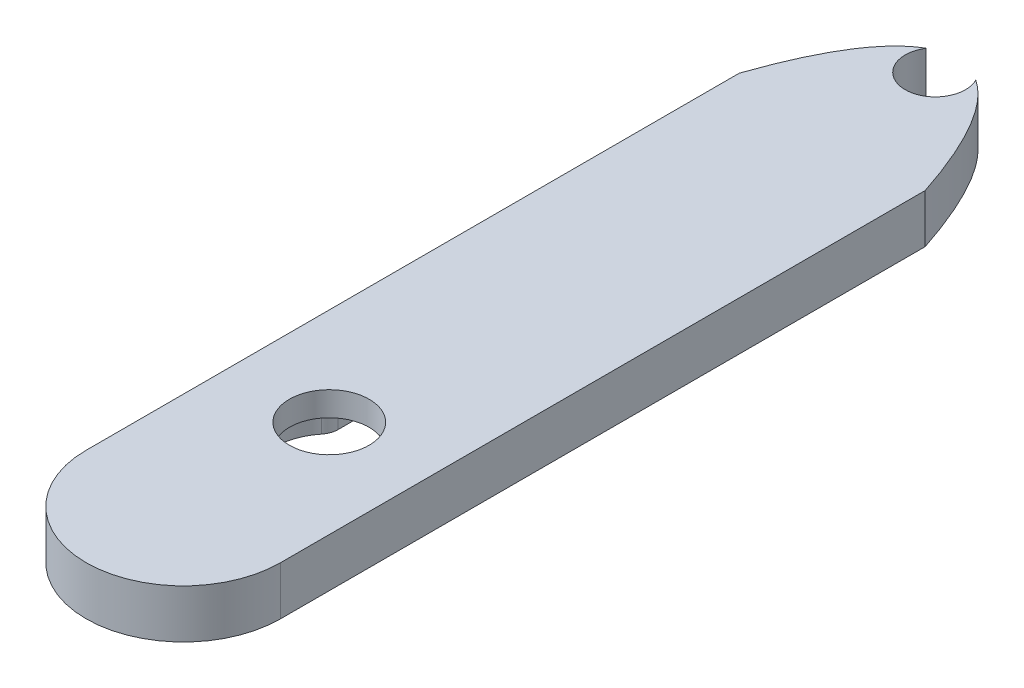
SolidWorks part; units mm, degrees
ref_plane "Front Plane" through (0, 0, 0) normal (0, 0, 1) x (1, 0, 0)
ref_plane "Top Plane" through (0, 0, 0) normal (0, 1, 0) x (1, 0, 0)
ref_plane "Right Plane" through (0, 0, 0) normal (1, 0, 0) x (0, 0, -1)
sketch "Sketch1" plane through (0, 0, 0) normal (0, 1, 0) x (1, 0, 0)
  line L0 (0, 0) -> (0, 12.7862) construction
  line L16 (-23.6152, 0) -> (23.6152, 0) construction
  line L22 (-3.8884, 4.0299) -> (-3.8884, 8.5053)
  line L23 (-3.8177, 9.3432) -> (-2.6646, 16.1267)
  line L24 (3.8299, 9.3786) -> (2.6768, 16.1621)
  line L25 (3.9006, 4.0181) -> (3.9006, 8.5407)
  line L26 (-3.8945, -4.024) -> (-3.8945, -8.5406)
  line L27 (-3.8238, -9.3786) -> (-2.6707, -16.1621)
  line L28 (3.8238, -9.3786) -> (2.6707, -16.1621)
  line L29 (3.8945, -4.024) -> (3.8945, -8.5406)
  line L30 (-10, 62.3) -> (-10, 25)
  line L31 (-7.5, 22.5) -> (7.5, 22.5)
  line L32 (-7.5, 22.5) -> (-7.5, -22.5)
  line L33 (-7.5, -22.5) -> (7.5, -22.5)
  line L34 (7.5, 22.5) -> (7.5, -22.5)
  line L35 (-7.5, 22.5) -> (7.5, -22.5) construction
  line L36 (-7.5, -22.5) -> (7.5, 22.5) construction
  line L41 (-10, 25) -> (10, 25)
  line L42 (-10, 25) -> (-10, -25)
  line L43 (-10, -25) -> (10, -25)
  line L44 (10, 25) -> (10, -25)
  line L45 (-10, 25) -> (10, 25)
  line L46 (-10, 25) -> (-10, 62.3)
  line L48 (10, 25) -> (10, 62.3)
  line L49 (10, 62.3) -> (10, 25)
  arc A8 (-2.5939, 16.9879) -> (2.606, 17) centre (0.006, 17) cw
  arc A9 (-2.6, -17) -> (2.6, -17) centre (0, -17) ccw
  circle A10 centre (0, 0) radius 5.6
  circle A11 centre (0, 0) radius 1.6
  circle A13 centre (0, 0) radius 4.1
  arc A14 (2.6, -17) -> (2.6707, -16.1621) centre (7.6, -17) cw
  arc A15 (-2.6707, -16.1621) -> (-2.6, -17) centre (-7.6, -17) cw
  arc A16 (-3.8945, -8.5406) -> (-3.8238, -9.3786) centre (1.1055, -8.5406) ccw
  arc A17 (3.8238, -9.3786) -> (3.8945, -8.5406) centre (-1.1055, -8.5406) ccw
  arc A18 (2.606, 17) -> (2.6768, 16.1621) centre (7.606, 17) ccw
  arc A19 (-2.6646, 16.1267) -> (-2.5939, 16.9879) centre (-7.5939, 16.9647) ccw
  arc A20 (3.8299, 9.3786) -> (3.9006, 8.5407) centre (-1.0994, 8.5407) cw
  arc A21 (-3.8884, 8.5053) -> (-3.8177, 9.3432) centre (1.1116, 8.5053) cw
  circle A22 centre (0, 62.3) radius 3.1
  arc A23 (-10, 62.3) -> (10, 62.3) centre (0, 62.3) cw
  point P14 (0, 0)
  point P49 (0, 19.6)
  point P50 (0, -19.6)
  dimension "D1" = 11.2
  dimension "D2" = 3.2
  dimension "D7" = 50
  dimension "D3" = 15
  dimension "D4" = 8.2
  dimension "D8" = 5
  dimension "D12" = 6.2
  dimension "D14" = 10
  dimension "D5" = 45
  dimension "D6" = 20
  dimension "D9" = 19.6
  dimension "D10" = 19.6
  dimension "D11" = 2.5
  dimension "D13" = 62.3
extrude "Boss-Extrude1" add sketch "Sketch1" against normal blind 2.2 contours L34 L31 L32 L33 A10 L29 L28 A9 L27 L26 L22 L23 A8 L24 L25 region at (0, 0, -22.0257)
extrude "Boss-Extrude2" add sketch "Sketch1<3>" against normal blind 2.5 contours L44 L41 L42 L43 L31 L34 L33 L32 | L34 L31 L32 L33 L22 A21 L23 A19 A8 A18 L24 A20 L25 A10 L29 A17 L28 A14 A9 A15 L27 A16 L26 region at (0, 0, -24.4615) region at (0, 0, -22.0257)
sketch "Sketch1<3>" plane through (0, 0, 0) normal (0, 1, 0) x (1, 0, 0) same geometry as "Sketch1"
extrude "Boss-Extrude3" add sketch "Sketch1<4>" along normal blind 2.5 contours L34 L31 L32 L33 A10 L29 L28 A9 L27 L26 L22 L23 A8 L24 L25 | A10 L25 L24 A8 L23 L22 | A10 L26 L27 A9 L28 L29 | L44 L41 L42 L43 L31 L34 L33 L32 | A10 A13 region at (0.0082, 0, -11.4698) region at (0.0082, 0, -5.4416) region at (0, 0, 11.4704) region at (0, 0, -24.4615) region at (0, 0, -22.0257)
sketch "Sketch1<4>" plane through (0, 0, 0) normal (0, 1, 0) x (1, 0, 0) same geometry as "Sketch1"
fillet "Fillet1" radius 2 4 edges at (3.8945, -1.25, 4.024) (-3.8945, -1.25, 4.024) (-3.8884, -1.25, -4.0299) (3.9006, -1.25, -4.0181)
extrude "Boss-Extrude4" add sketch "Sketch1<5>" along normal mid plane 5 contours A23 L30 L41 L48 A22 region at (0, 0, -47.1248)
sketch "Sketch1<5>" plane through (0, 0, 0) normal (0, 1, 0) x (1, 0, 0) same geometry as "Sketch1"
fillet "Fillet2" radius 10 2 edges at (10, 0, 25) (-10, 0, 25)
sketch "Sketch2" plane through (0, -2.5, 0) normal (0, -1, 0) x (1, 0, 0)
  line L30 (5.7735, -40.7449) -> (-2.8868, -35.7449)
  line L31 (5.9735, -40.7449) -> (-2.9868, -35.5717)
  line L32 (-2.8868, -45.7449) -> (5.7735, -40.7449)
  line L33 (-2.9868, -45.9181) -> (5.9735, -40.7449)
  line L34 (-2.8868, -35.7449) -> (-2.8868, -45.7449)
  line L35 (-2.9868, -35.5717) -> (-2.9868, -45.9181)
  line L36 (5.7735, -24.7449) -> (-2.8868, -19.7449)
  line L37 (5.9735, -24.7449) -> (-2.9868, -19.5717)
  line L38 (-2.8868, -29.7449) -> (5.7735, -24.7449)
  line L39 (-2.9868, -29.9181) -> (5.9735, -24.7449)
  line L40 (-2.8868, -19.7449) -> (-2.8868, -29.7449)
  line L41 (-2.9868, -19.5717) -> (-2.9868, -29.9181)
  line L48 (-3.0868, -48.7449) -> (5.8735, -43.5717)
  line L49 (5.8735, -43.5717) -> (5.8735, -53.9181)
  line L50 (5.8735, -53.9181) -> (-3.0868, -48.7449)
  line L51 (5.7735, -53.7449) -> (-2.8868, -48.7449)
  line L52 (-2.8868, -48.7449) -> (5.7735, -43.7449)
  line L53 (5.7735, -43.7449) -> (5.7735, -53.7449)
  line L54 (-3.0868, -32.7449) -> (5.8735, -27.5717)
  line L55 (5.8735, -27.5717) -> (5.8735, -37.9181)
  line L56 (5.8735, -37.9181) -> (-3.0868, -32.7449)
  line L57 (5.7735, -37.7449) -> (-2.8868, -32.7449)
  line L58 (-2.8868, -32.7449) -> (5.7735, -27.7449)
  line L59 (5.7735, -27.7449) -> (5.7735, -37.7449)
extrude "Cut-Extrude2" cut sketch "Sketch2" against normal blind 4
sketch "Sketch3" plane through (0, -2.5, 0) normal (0, -1, 0) x (1, 0, 0)
  line L20 (10, -62.3) -> (10, 15)
  line L21 (-10, 15) -> (-10, -62.3)
  line L22 (10, -51.2562) -> (10, 15)
  line L23 (-10, 15) -> (-10, -52.1476)
  arc A45 (10, 15) -> (0, 25) centre (0, 15) ccw
  arc A46 (0, 25) -> (-10, 15) centre (0, 15) ccw
  arc A47 (-10, -62.3) -> (10, -62.3) centre (0, -62.3) ccw
  arc A48 (10, 15) -> (0, 25) centre (0, 15) ccw
  arc A49 (0, 25) -> (-10, 15) centre (0, 15) ccw
  spline S0 degree 3 poles (959.2317, 518.5266) (-16.5091, 332.1894) (-6.4546, 283.312) (0.5285, 233.2241) (0.8468, 230.9312) (1.2834, 227.7409) (1.8334, 223.673) (2.4857, 218.7524) (3.2315, 213.0095) (4.059, 206.4797) (4.9572, 199.2032) (5.9128, 191.225) (6.9142, 182.5942) (7.9479, 173.3639) (9.0011, 163.5912) (10.0607, 153.3362) (11.1132, 142.6623) (12.1437, 131.6352) (13.1387, 120.3229) (14.0816, 108.7952) (14.957, 97.123) (15.7486, 85.3783) (16.4398, 73.6335) (17.0134, 61.9609) (17.4538, 50.4326) (17.7468, 39.1193) (17.878, 28.091) (17.8371, 17.4154) (17.6161, 7.1583) (17.2095, -2.6172) (16.6161, -11.8508) (15.8378, -20.4858) (14.8806, -28.4694) (13.7526, -35.7529) (12.4657, -42.2922) (11.0345, -48.0489) (9.4728, -52.9904) (7.7952, -57.0915) (6.013, -60.3391) (4.1228, -62.7283) (2.0788, -64.2586) (-0.15, -64.7955) (-2.3788, -64.2586) (-4.4228, -62.7283) (-6.313, -60.3391) (-8.0952, -57.0915) (-9.7728, -52.9904) (-11.3345, -48.0489) (-12.7657, -42.2922) (-14.0526, -35.7529) (-15.1806, -28.4694) (-16.1378, -20.4858) (-16.9161, -11.8508) (-17.5095, -2.6172) (-17.9161, 7.1583) (-18.1371, 17.4154) (-18.178, 28.091) (-18.0468, 39.1193) (-17.7538, 50.4326) (-17.3134, 61.9609) (-16.7398, 73.6335) (-16.0486, 85.3783) (-15.257, 97.123) (-14.3816, 108.7952) (-13.4387, 120.3229) (-12.4437, 131.6352) (-11.4132, 142.6623) (-10.3607, 153.3362) (-9.3011, 163.5912) (-8.2479, 173.3639) (-7.2142, 182.5942) (-6.2128, 191.225) (-5.2572, 199.2032) (-4.359, 206.4797) (-3.5315, 213.0095) (-2.7857, 218.7524) (-2.1334, 223.673) (-1.5834, 227.7409) (-1.1468, 230.9312) (-0.8285, 233.2241) (6.1546, 283.3123) (16.2092, 332.1901) (-959.5521, 518.5305) knots -0.241187 -0.241187 -0.241187 -0.241187 0.000763 0.003048 0.006841 0.012116 0.018841 0.026973 0.03646 0.047243 0.059254 0.072417 0.086651 0.101866 0.117969 0.134858 0.152428 0.170572 0.189175 0.208122 0.227297 0.24658 0.265853 0.284997 0.303895 0.322433 0.340499 0.357984 0.374788 0.390812 0.405965 0.420162 0.433328 0.445394 0.456301 0.466004 0.474472 0.481696 0.487704 0.492583 0.496544 0.5 0.503456 0.507417 0.512296 0.518304 0.525528 0.533996 0.543699 0.554606 0.566672 0.579838 0.594035 0.609188 0.625212 0.642016 0.659501 0.677567 0.696105 0.715003 0.734147 0.75342 0.772703 0.791878 0.810825 0.829428 0.847572 0.865142 0.882031 0.898134 0.913349 0.927583 0.940746 0.952757 0.96354 0.973027 0.981159 0.987884 0.993159 0.996952 0.999237 1.241188 1.241188 1.241188 1.241188 only from (0.228, 235.3752) to (-0.528, 235.3752) construction
  spline S1 degree 3 poles (10, -51.2562) (9.7851, -51.91) (9.079, -53.953) (7.7952, -57.0915) (6.013, -60.3391) (4.1228, -62.7283) (2.0788, -64.2586) (-0.15, -64.7955) (-2.3788, -64.2586) (-4.4228, -62.7283) (-6.313, -60.3391) (-8.0952, -57.0915) (-9.2601, -54.2436) (-9.8779, -52.5018) (-10, -52.1476) knots 0.471098 0.471098 0.471098 0.471098 0.474472 0.481696 0.487704 0.492583 0.496544 0.5 0.503456 0.507417 0.512296 0.518304 0.525528 0.527365 0.527365 0.527365 0.527365
  dimension "D1" = 0
extrude "Cut-Extrude3" cut sketch "Sketch3" against normal through all flip side to cut
